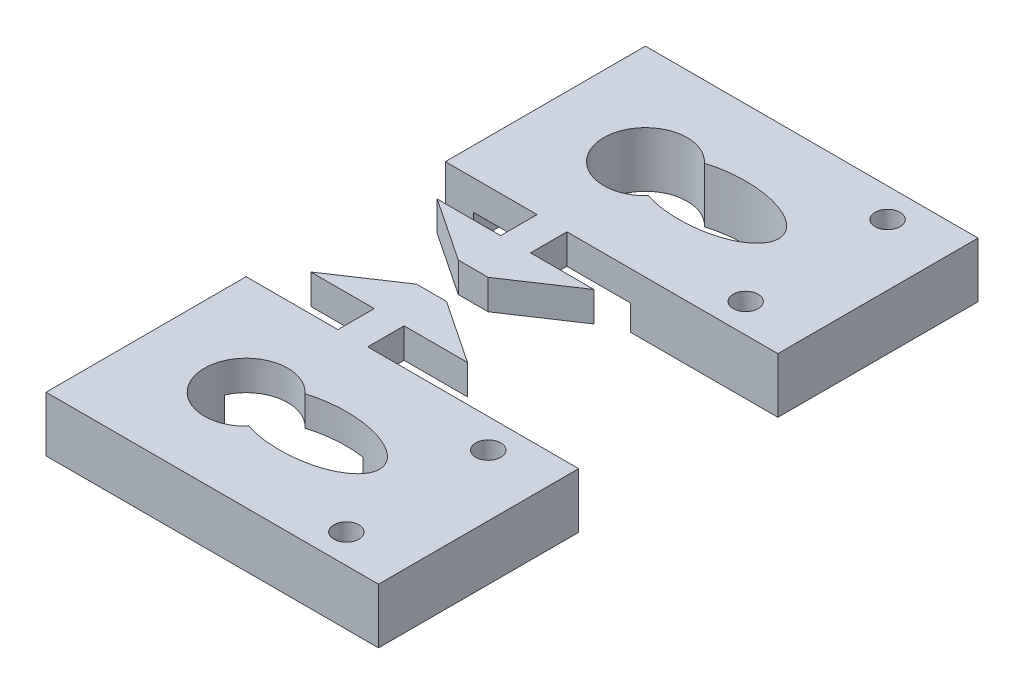
SolidWorks part; units mm, degrees
ref_plane "Front" through (0, 0, 0) normal (0, 0, 1) x (1, 0, 0)
ref_plane "Top" through (0, 0, 0) normal (0, 1, 0) x (1, 0, 0)
ref_plane "Right" through (0, 0, 0) normal (1, 0, 0) x (0, 0, -1)
sketch "Sketch1" plane through (0, 0, 0) normal (0, 1, 0) x (1, 0, 0)
  line L0 (-1.7907, 2.1825) -> (-9.398, 2.1825)
  line L2 (-1.7907, -2.1825) -> (-1.7907, 2.1825)
  line L4 (1.7907, -2.1825) -> (1.7907, 2.1825)
  line L7 (-9.398, 2.1825) -> (-1.7907, 7.2625)
  line L8 (-1.7907, 7.2625) -> (1.7907, 7.2625)
  line L9 (1.7907, 7.2625) -> (9.398, 2.1825)
  line L10 (9.398, 2.1825) -> (1.7907, 2.1825)
  line L11 (1.7907, -2.1825) -> (27.088, -2.1825)
  line L12 (-1.7907, -2.1825) -> (-12.79, -2.1825)
  line L13 (-12.79, -2.1825) -> (-12.79, -26.1825)
  line L14 (-12.79, -26.1825) -> (27.088, -26.1825)
  line L15 (27.088, -26.1825) -> (27.088, -2.1825)
  line L16 (27.088, -2.1825) -> (1.7907, -2.1825)
  point P0 (0, 0)
  point P17 (0, 7.2625)
  point P24 (1.7907, 0)
  dimension "D1" = 18.796
  dimension "D2" = 3.5814
  dimension "D3" = 39.878
  dimension "D4" = 24
  dimension "D5" = 5.08
  dimension "D6" = 12.79
  dimension "D7" = 4.365
extrude "Boss-Extrude1" add sketch "Sketch1" along normal blind 3.5814 contours L14 L15 L11 L4 L10 L9 L8 L7 L0 L2 L12 L13 region at (6.6458, 0, 12.9552)
ref_plane "Plane1" through (0, 1.7907, 0) normal (0, 1, 0) x (1, 0, 0)
sketch "Sketch7" plane through (0, 0, 0) normal (0, 1, 0) x (1, 0, 0)
  line L1 (-12.79, -2.1825) -> (27.088, -2.1825)
  line L2 (-12.79, -2.1825) -> (-12.79, -26.1825)
  line L3 (-12.79, -26.1825) -> (27.088, -26.1825)
  line L4 (27.088, -2.1825) -> (27.088, -26.1825)
extrude "Boss-Extrude2" add sketch "Sketch7" along normal blind 3.035 and the other way blind 3.035
sketch "Sketch5" plane through (0, 3.5814, 0) normal (0, 1, 0) x (1, 0, 0)
  line L0 (-12.79, -2.1825) -> (-12.79, -26.1825) construction
  line L1 (-12.79, -14.1825) -> (27.088, -14.1825) construction
  line L2 (27.088, -26.1825) -> (27.088, -2.1825) construction
  circle A0 centre (-0.79, -14.1825) radius 5
  circle A1 centre (19.738, -22.6915) radius 1.5
  circle A2 centre (19.738, -5.6735) radius 1.5
  ellipse E0 centre (7.21, -14.1825) end of major axis (-0.79, -14.1825) minor radius 4
  point P5 (-12.79, -14.1825)
  dimension "D2" = 10
  dimension "D6" = 3
  dimension "D1" = 12
  dimension "D3" = 8
  dimension "D4" = 16
  dimension "D5" = 17.018
  dimension "D7" = 7.35
extrude "Cut-Extrude3" cut sketch "Sketch5" against normal through all both and the other way through all contours A0 L1 E0 | E0 L1 A0 | A0 L1 E0 | L1 A0 E0 | L1 E0 A0 | L1 A0 E0 | A1 | A2 region at (1.9147, 3.5814, 12.8743) region at (-1.952, 3.5814, 16.6542) region at (1.9147, 3.5814, 15.4907) region at (-1.952, 3.5814, 11.7108) region at (8.8346, 3.5814, 12.3654) region at (8.8346, 3.5814, 15.9996) region at (19.738, 3.5814, 22.6915)
ref_plane "Plane2" through (0, 0, -17.2625) normal (0, 0, -1) x (-1, 0, 0)
sketch "Sketch8" plane through (0, 0, 2.1825) normal (0, 0, -1) x (-1, 0, 0)
  line L0 (-27.088, -3.035) -> (12.79, -3.035) construction
  line L1 (-9.398, 0) -> (9.398, 0)
  line L2 (-9.398, 0) -> (-9.398, -3.035)
  line L3 (-9.398, -3.035) -> (9.398, -3.035)
  line L4 (9.398, 0) -> (9.398, -3.035)
  line L5 (-9.398, 3.5814) -> (-9.398, 0) construction
  line L6 (9.398, 3.5814) -> (9.398, 0) construction
  line L7 (-1.7907, 0) -> (1.7907, 0) construction
extrude "Cut-Extrude4" cut sketch "Sketch8" against normal blind 10
ref_plane "Plane3" through (0, 0, -9.7625) normal (0, 0, -1) x (-1, 0, 0)
mirror "Mirror2" about plane through (0, 0, -9.7625) normal (0, 0, -1) of bodies 108
